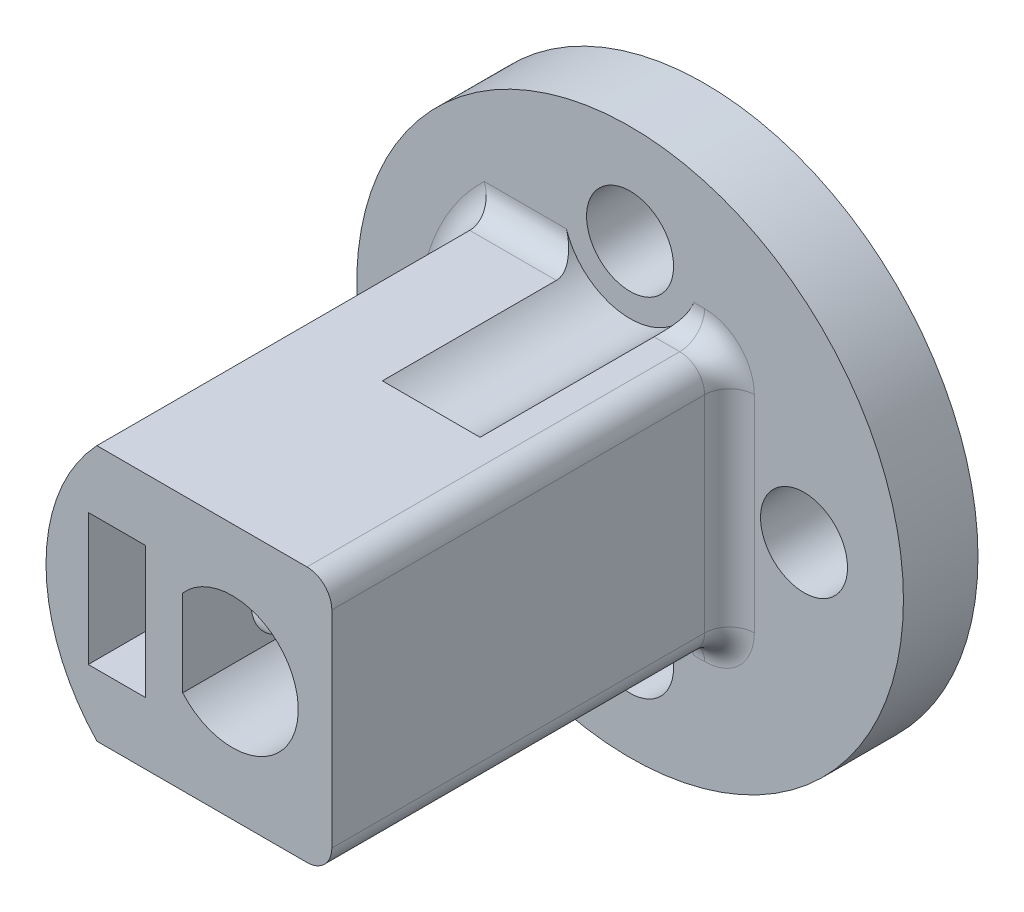
SolidWorks part; units mm, degrees
ref_plane "前视基准面" through (0, 0, 0) normal (0, 0, 1) x (1, 0, 0)
ref_plane "上视基准面" through (0, 0, 0) normal (0, 1, 0) x (1, 0, 0)
ref_plane "右视基准面" through (0, 0, 0) normal (1, 0, 0) x (0, 0, -1)
sketch "草图1" plane through (0, 0, 0) normal (0, 0, 1) x (1, 0, 0)
  circle A0 centre (0, 0) radius 11
  circle A1 centre (0, 0) radius 7 construction
  circle A2 centre (0, 7) radius 1.75
  circle A3 centre (7, 0) radius 1.75
  circle A4 centre (0, -7) radius 1.75
  circle A5 centre (-7, 0) radius 1.75
  point P15 (0, 0)
  dimension "D1" = 22
  dimension "D2" = 14
  dimension "D3" = 3.5
  dimension "D4" = 4
extrude "凸台-拉伸1" add sketch "草图1" along normal blind 3
sketch "草图2" plane through (0, 0, 3) normal (0, 0, 1) x (1, 0, 0)
  line L0 (-2, 1.7385) -> (-2, -1.7385)
  circle A1 centre (0, 0) radius 7.5
  arc A2 (-2, 1.7385) -> (2.5096, 0.8511) centre (0, 0) cw
  arc A3 (-0.4378, -2.6136) -> (2.5096, 0.8511) centre (0, 0) ccw
  arc A4 (-2, -1.7385) -> (-0.4378, -2.6136) centre (0, 0) ccw
  dimension "D3" = 15
  dimension "D2" = 2
extrude "凸台-拉伸2" add sketch "草图2" along normal blind 16
sketch "草图10" plane through (0, 0, 19) normal (0, 0, 1) x (1, 0, 0)
  line L0 (0, 0) -> (-13.5627, 0) construction
  line L1 (-3.5, -2.65) -> (-3.5, 2.65)
  line L2 (-3.5, 2.65) -> (-5.8, 2.65)
  line L3 (-5.8, 2.65) -> (-5.8, -2.65)
  line L4 (-5.8, -2.65) -> (-3.5, -2.65)
  line L5 (-2, 1.7385) -> (-2, -1.7385) construction
  point P7 (-3.5, 0)
  dimension "D1" = 5.3
  dimension "D2" = 2.3
  dimension "D3" = 1.5
extrude "切除-拉伸4" cut sketch "草图10" against normal up to surface (16 mm away) up to face at (0, 0, 3)
sketch "草图12" plane through (0, 0, 19) normal (0, 0, 1) x (1, 0, 0)
  line L0 (-5.4523, 5.15) -> (4, 5.15)
  line L1 (4, 5.15) -> (4, -5.15)
  line L2 (0, 0) -> (4, 0) construction
  line L3 (-5.4523, -5.15) -> (4, -5.15)
  line L4 (-3.5, 2.65) -> (-5.8, 2.65) construction
  circle A0 centre (0, 0) radius 7.5 construction
  arc A3 (-5.4523, -5.15) -> (-5.4523, 5.15) centre (0, 0) ccw
  dimension "D1" = 2.5
  dimension "D2" = 4
extrude "切除-拉伸5" cut sketch "草图12" against normal up to surface (16 mm away) up to face at (0, 0, 3)
sketch "草图13" plane through (0, 0, 3) normal (0, 0, 1) x (1, 0, 0)
  circle A0 centre (0, 7) radius 2.7
  circle A1 centre (7, 0) radius 2.7
  circle A2 centre (0, -7) radius 2.7
  circle A3 centre (-7, 0) radius 2.7
  point P12 (0, 0)
  dimension "D1" = 5.4
  dimension "D2" = 4
extrude "切除-拉伸6" cut sketch "草图13" along normal offset from surface (8 mm away) 8 up to face at (-1.2381, 0, 19)
fillet "圆角1" radius 1 9 edges at (4, 5.15, 11) (4, -5.15, 11) (-3.7094, -5.15, 3) (-6.3441, -4.0003, 3) (-6.3441, 4.0003, 3) (-3.7094, 5.15, 3) (2.9833, 5.15, 3) (2.9833, -5.15, 3) (4, 0, 3)
ref_plane "基准面1" through (-10.8, 0, 0) normal (1, 0, 0) x (0, 0, -1)
sketch "草图15" plane through (-10.8, 0, 0) normal (1, 0, 0) x (0, 0, -1)
  line L0 (-11, -2.7) -> (-11, 2.7) construction
  circle A0 centre (-14.5, 0) radius 1.75
  point P4 (-11, 0)
  dimension "D1" = 3.5
  dimension "D2" = 3.5
extrude "切除-拉伸7" cut sketch "草图15" along normal blind 10
